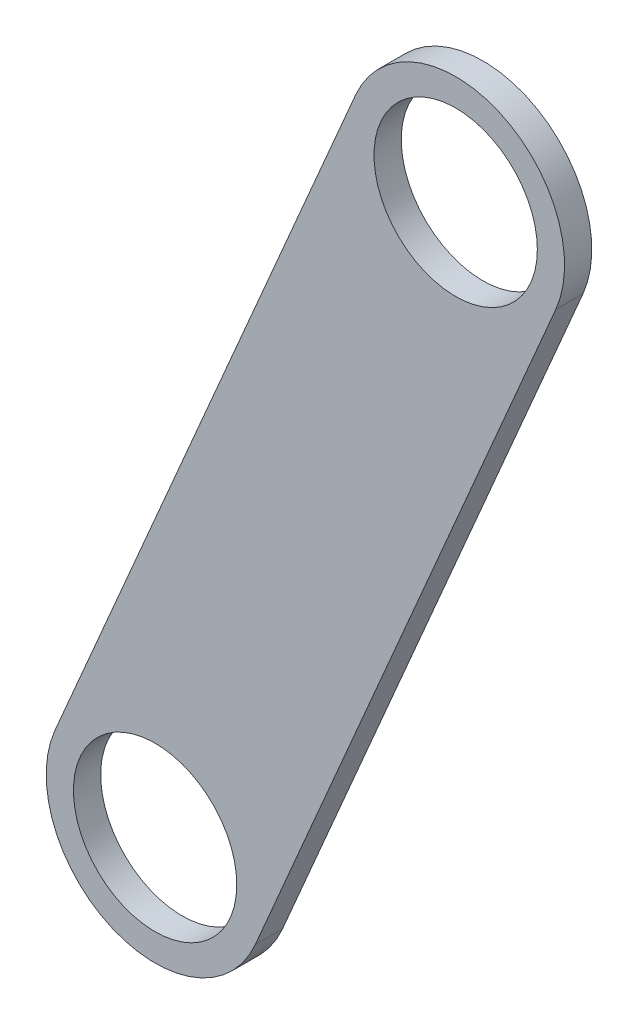
SolidWorks part; units mm, degrees
ref_plane "Front Plane" through (0, 0, 0) normal (0, 0, 1) x (1, 0, 0)
ref_plane "Top Plane" through (0, 0, 0) normal (0, 1, 0) x (1, 0, 0)
ref_plane "Right Plane" through (0, 0, 0) normal (1, 0, 0) x (0, 0, -1)
sketch "Esquisse1" plane through (0, 0, 0) normal (0, 0, 1) x (1, 0, 0)
  line L0 (31.7651, -5.8702) -> (20.723, -31.6009) construction
  line L3 (35.4409, -7.4476) -> (24.3988, -33.1784)
  line L4 (28.0893, -4.2927) -> (17.0472, -30.0235)
  arc A4 (35.4409, -7.4476) -> (28.0893, -4.2927) centre (31.7651, -5.8702) ccw
  arc A5 (17.0472, -30.0235) -> (24.3988, -33.1784) centre (20.723, -31.6009) ccw
  circle A6 centre (31.7651, -5.8702) radius 3
  circle A7 centre (20.723, -31.6009) radius 3
  point P4 (26.2441, -18.7356)
  dimension "D2" = 6
  dimension "D1" = 8
base flange "Tôle de base pliée1" sketch "Esquisse1" thickness 1 reverse thickness direction yes parameters "D1"=0.7366
sketch "Bend-Lines1" [suppressed] plane through (0, 0, 0) normal (0, 1, 0) x (1, 0, 0)
sketch "Bounding-Box1" [suppressed] plane through (0, 0, 0) normal (0, 1, 0) x (1, 0, 0)
sheet metal parameters "Sheet-Metal1" thickness 1 parameters "D1"=0.7366
flat pattern "Flat-Pattern1" [suppressed]
sketch "Bend-Lines2" plane through (0, 0, 0) normal (0, 1, 0) x (1, 0, 0)
sketch3d "Bounding-Box2" [suppressed]
  line L0 (8.9437, -30.984, 0) -> (-5.2533, 2.0983, 0) construction
  line L1 (16.2954, -27.8291, 0) -> (2.0984, 5.2532, 0) construction
  line L2 (8.9437, -30.984, 0) -> (16.2954, -27.8291, 0) construction
  line L3 (-5.2533, 2.0983, 0) -> (2.0984, 5.2532, 0) construction
